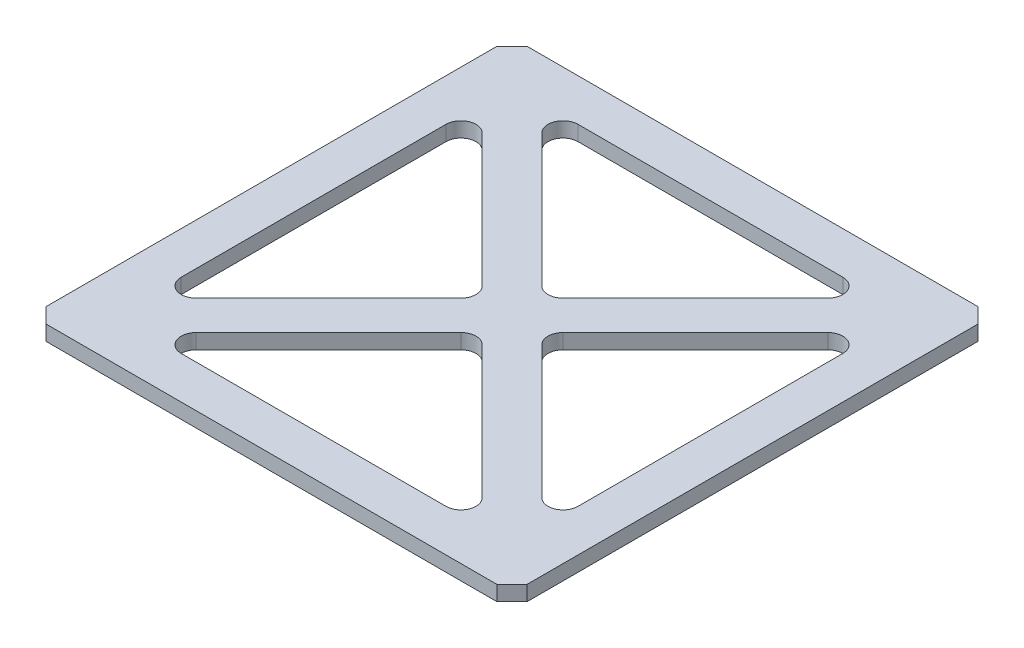
SolidWorks part; units mm, degrees
ref_plane "Front Plane" through (0, 0, 0) normal (0, 0, 1) x (1, 0, 0)
ref_plane "Top Plane" through (0, 0, 0) normal (0, 1, 0) x (1, 0, 0)
ref_plane "Right Plane" through (0, 0, 0) normal (1, 0, 0) x (0, 0, -1)
sketch "Sketch1" plane through (0, 0, 0) normal (0, 1, 0) x (1, 0, 0)
  line L0 (0, 196.85) -> (6.35, 203.2)
  line L1 (6.35, 0) -> (196.85, 0)
  line L2 (0, 6.35) -> (0, 196.85)
  line L3 (6.35, 203.2) -> (196.85, 203.2)
  line L4 (203.2, 6.35) -> (203.2, 196.85)
  line L5 (196.85, 203.2) -> (203.2, 196.85)
  line L6 (196.85, 0) -> (203.2, 6.35)
  line L7 (0, 6.35) -> (6.35, 0)
  point P0 (0, 0)
  point P1 (203.2, 203.2)
  point P2 (0, 203.2)
  point P3 (203.2, 0)
  dimension "D1" = 203.2
  dimension "D2" = 203.2
extrude "Boss-Extrude1" add sketch "Sketch1" along normal blind 6.35
sketch "Sketch2" plane through (0, 6.35, 0) normal (0, 1, 0) x (1, 0, 0)
  line L0 (203.2, 6.35) -> (203.2, 196.85) construction
  line L1 (45.6826, 185.42) -> (157.5174, 185.42)
  line L2 (17.78, 157.5174) -> (17.78, 45.6826)
  line L3 (45.6826, 17.78) -> (157.5174, 17.78)
  line L4 (185.42, 157.5174) -> (185.42, 45.6826)
  line L5 (196.85, 203.2) -> (6.35, 203.2) construction
  line L6 (0, 196.85) -> (0, 6.35) construction
  line L7 (3.175, 3.175) -> (200.025, 200.025) construction
  line L8 (3.175, 200.025) -> (101.6, 101.6) construction
  line L9 (28.6201, 162.0075) -> (84.5375, 106.0901)
  line L10 (41.1925, 28.6201) -> (97.1099, 84.5375)
  line L11 (41.1925, 174.5799) -> (97.1099, 118.6625)
  line L12 (28.6201, 41.1925) -> (84.5375, 97.1099)
  line L13 (9.4612, -3.1112) -> (206.3112, 193.7388) construction
  line L14 (-3.1112, 9.4612) -> (193.7388, 206.3112) construction
  line L15 (9.4612, 206.3112) -> (206.3112, 9.4612) construction
  line L16 (-3.1112, 193.7388) -> (193.7388, -3.1112) construction
  line L17 (118.6625, 106.0901) -> (174.5799, 162.0075)
  line L18 (101.6, 101.6) -> (200.025, 3.175) construction
  line L19 (3.175, 200.025) -> (200.025, 3.175) construction
  line L20 (118.6625, 97.1099) -> (174.5799, 41.1925)
  line L21 (106.0901, 118.6625) -> (162.0075, 174.5799)
  line L22 (106.0901, 84.5375) -> (162.0075, 28.6201)
  line L23 (6.35, 0) -> (196.85, 0) construction
  line L24 (6.35, 203.2) -> (0, 196.85) construction
  line L25 (203.2, 196.85) -> (196.85, 203.2) construction
  line L26 (196.85, 0) -> (203.2, 6.35) construction
  arc A0 (185.42, 45.6826) -> (174.5799, 41.1925) centre (179.07, 45.6826) cw
  arc A1 (185.42, 157.5174) -> (174.5799, 162.0075) centre (179.07, 157.5174) ccw
  arc A2 (157.5174, 185.42) -> (162.0075, 174.5799) centre (157.5174, 179.07) cw
  arc A3 (118.6625, 106.0901) -> (118.6625, 97.1099) centre (123.1526, 101.6) ccw
  arc A4 (41.1925, 28.6201) -> (45.6826, 17.78) centre (45.6826, 24.13) ccw
  arc A5 (157.5174, 17.78) -> (162.0075, 28.6201) centre (157.5174, 24.13) ccw
  arc A6 (28.6201, 41.1925) -> (17.78, 45.6826) centre (24.13, 45.6826) cw
  arc A7 (84.5375, 97.1099) -> (84.5375, 106.0901) centre (80.0474, 101.6) ccw
  arc A8 (28.6201, 162.0075) -> (17.78, 157.5174) centre (24.13, 157.5174) ccw
  arc A9 (41.1925, 174.5799) -> (45.6826, 185.42) centre (45.6826, 179.07) cw
  arc A10 (97.1099, 84.5375) -> (106.0901, 84.5375) centre (101.6, 80.0474) cw
  arc A11 (97.1099, 118.6625) -> (106.0901, 118.6625) centre (101.6, 123.1526) ccw
  point P10 (0, 101.6)
  point P11 (17.78, 101.6)
  point P32 (0, 0)
  point P36 (0, 0)
  point P37 (101.6, 17.78)
  point P38 (0, 0)
  point P39 (122.5324, 101.6)
  point P40 (101.6, 101.6)
  point P41 (0, 0)
  point P50 (114.1724, 101.6)
  point P65 (101.6, 89.0276)
  point P68 (101.6, 114.1724)
  point P69 (0, 0)
  point P72 (0, 0)
  point P75 (0, 0)
  dimension "D7" = 6.35
  dimension "D8" = 6.35
  dimension "D9" = 6.35
  dimension "D1" = 17.78
  dimension "D2" = 17.78
  dimension "D3" = 8.89
  dimension "D5" = 17.78
  dimension "D6" = 17.78
  dimension "D4" = 8.89
extrude "Cut-Extrude1" cut sketch "Sketch2" against normal through all
